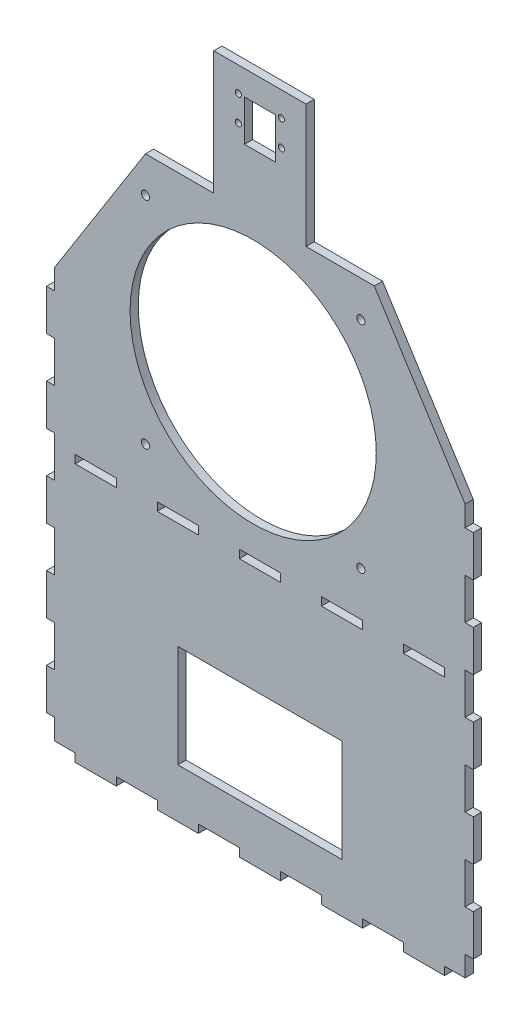
SolidWorks part; units mm, degrees
ref_plane "Přední rovina" through (0, 0, 0) normal (0, 0, 1) x (1, 0, 0)
ref_plane "Horní rovina" through (0, 0, 0) normal (0, 1, 0) x (1, 0, 0)
ref_plane "Pravá rovina" through (0, 0, 0) normal (1, 0, 0) x (0, 0, -1)
sketch "Skica1" plane through (0, 0, 0) normal (0, 0, 1) x (1, 0, 0)
  line L0 (-22.5981, -113.24) -> (-22.5981, -95.4761)
  line L1 (-122.5981, -113.24) -> (77.4019, -113.24)
  line L2 (-122.5981, -113.24) -> (-122.5981, 156.76)
  line L3 (-122.5981, 156.76) -> (77.4019, 156.76)
  line L4 (77.4019, -113.24) -> (77.4019, 156.76)
  line L5 (-112.5981, -113.24) -> (-92.5981, -113.24)
  line L6 (-112.5981, -113.24) -> (-112.5981, -117.24)
  line L7 (-112.5981, -117.24) -> (-92.5981, -117.24)
  line L8 (-92.5981, -113.24) -> (-92.5981, -117.24)
  line L9 (-72.5981, -113.24) -> (-52.5981, -113.24)
  line L10 (-72.5981, -113.24) -> (-72.5981, -117.24)
  line L11 (-72.5981, -117.24) -> (-52.5981, -117.24)
  line L12 (-52.5981, -113.24) -> (-52.5981, -117.24)
  line L13 (-32.5981, -113.24) -> (-12.5981, -113.24)
  line L14 (-32.5981, -113.24) -> (-32.5981, -117.24)
  line L15 (-32.5981, -117.24) -> (-12.5981, -117.24)
  line L16 (-12.5981, -113.24) -> (-12.5981, -117.24)
  line L17 (27.4019, -117.24) -> (7.4019, -117.24)
  line L18 (7.4019, -113.24) -> (7.4019, -117.24)
  line L19 (27.4019, -113.24) -> (7.4019, -113.24)
  line L20 (27.4019, -113.24) -> (27.4019, -117.24)
  line L21 (67.4019, -117.24) -> (47.4019, -117.24)
  line L22 (47.4019, -113.24) -> (47.4019, -117.24)
  line L23 (67.4019, -113.24) -> (47.4019, -113.24)
  line L24 (67.4019, -113.24) -> (67.4019, -117.24)
  line L25 (77.4019, 36.76) -> (81.4019, 36.76)
  line L26 (-122.5981, -103.24) -> (-126.5981, -103.24)
  line L27 (-122.5981, -103.24) -> (-122.5981, -83.24)
  line L28 (-122.5981, -83.24) -> (-126.5981, -83.24)
  line L29 (-126.5981, -103.24) -> (-126.5981, -83.24)
  line L30 (-122.5981, -63.24) -> (-126.5981, -63.24)
  line L31 (-122.5981, -63.24) -> (-122.5981, -43.24)
  line L32 (-122.5981, -43.24) -> (-126.5981, -43.24)
  line L33 (-126.5981, -63.24) -> (-126.5981, -43.24)
  line L34 (-122.5981, -23.24) -> (-126.5981, -23.24)
  line L35 (-122.5981, -23.24) -> (-122.5981, -3.24)
  line L36 (-122.5981, -3.24) -> (-126.5981, -3.24)
  line L37 (-126.5981, -23.24) -> (-126.5981, -3.24)
  line L38 (-122.5981, 16.76) -> (-126.5981, 16.76)
  line L39 (-122.5981, 16.76) -> (-122.5981, 36.76)
  line L40 (-122.5981, 36.76) -> (-126.5981, 36.76)
  line L41 (-126.5981, 16.76) -> (-126.5981, 36.76)
  line L42 (81.4019, 16.76) -> (81.4019, 36.76)
  line L43 (77.4019, 16.76) -> (81.4019, 16.76)
  line L44 (77.4019, 16.76) -> (77.4019, 36.76)
  line L45 (77.4019, -3.24) -> (81.4019, -3.24)
  line L46 (81.4019, -23.24) -> (81.4019, -3.24)
  line L47 (77.4019, -23.24) -> (81.4019, -23.24)
  line L48 (77.4019, -23.24) -> (77.4019, -3.24)
  line L49 (77.4019, -43.24) -> (81.4019, -43.24)
  line L50 (81.4019, -63.24) -> (81.4019, -43.24)
  line L51 (77.4019, -63.24) -> (81.4019, -63.24)
  line L52 (77.4019, -63.24) -> (77.4019, -43.24)
  line L53 (77.4019, -83.24) -> (81.4019, -83.24)
  line L54 (81.4019, -103.24) -> (81.4019, -83.24)
  line L55 (77.4019, -103.24) -> (81.4019, -103.24)
  line L56 (77.4019, -103.24) -> (77.4019, -83.24)
  line L57 (-78.3799, 156.76) -> (-122.5981, 86.76)
  line L58 (-112.5981, 12.76) -> (-92.5981, 12.76)
  line L59 (-112.5981, 12.76) -> (-112.5981, 8.76)
  line L60 (-112.5981, 8.76) -> (-92.5981, 8.76)
  line L61 (-92.5981, 12.76) -> (-92.5981, 8.76)
  line L62 (-72.5981, 12.76) -> (-52.5981, 12.76)
  line L63 (-72.5981, 12.76) -> (-72.5981, 8.76)
  line L64 (-72.5981, 8.76) -> (-52.5981, 8.76)
  line L65 (-52.5981, 12.76) -> (-52.5981, 8.76)
  line L66 (-32.5981, 12.76) -> (-12.5981, 12.76)
  line L67 (-32.5981, 12.76) -> (-32.5981, 8.76)
  line L68 (-32.5981, 8.76) -> (-12.5981, 8.76)
  line L69 (-12.5981, 12.76) -> (-12.5981, 8.76)
  line L70 (7.4019, 12.76) -> (27.4019, 12.76)
  line L71 (7.4019, 12.76) -> (7.4019, 8.76)
  line L72 (7.4019, 8.76) -> (27.4019, 8.76)
  line L73 (27.4019, 12.76) -> (27.4019, 8.76)
  line L74 (47.4019, 12.76) -> (67.4019, 12.76)
  line L75 (47.4019, 12.76) -> (47.4019, 8.76)
  line L76 (47.4019, 8.76) -> (67.4019, 8.76)
  line L77 (67.4019, 12.76) -> (67.4019, 8.76)
  line L78 (-122.5981, 56.76) -> (-126.5981, 56.76)
  line L79 (-122.5981, 56.76) -> (-122.5981, 76.76)
  line L80 (-122.5981, 76.76) -> (-126.5981, 76.76)
  line L81 (-126.5981, 56.76) -> (-126.5981, 76.76)
  line L82 (33.1836, 156.76) -> (77.4019, 86.76)
  line L83 (77.4019, 76.76) -> (81.4019, 76.76)
  line L84 (81.4019, 56.76) -> (81.4019, 76.76)
  line L85 (77.4019, 56.76) -> (81.4019, 56.76)
  line L86 (77.4019, 56.76) -> (77.4019, 76.76)
  line L88 (-45.0981, 156.76) -> (-0.0981, 156.76)
  line L89 (-45.0981, 156.76) -> (-45.0981, 216.8991)
  line L90 (-45.0981, 216.8991) -> (-0.0981, 216.8991)
  line L91 (-0.0981, 156.76) -> (-0.0981, 216.8991)
  line L92 (-30.0981, 204.8991) -> (-15.0981, 204.8991)
  line L93 (-30.0981, 204.8991) -> (-30.0981, 184.8991)
  line L94 (-30.0981, 184.8991) -> (-15.0981, 184.8991)
  line L95 (-15.0981, 204.8991) -> (-15.0981, 184.8991)
  line L96 (-62.5981, -93.24) -> (17.4019, -93.24)
  line L97 (-62.5981, -93.24) -> (-62.5981, -43.24)
  line L98 (-62.5981, -43.24) -> (17.4019, -43.24)
  line L99 (17.4019, -93.24) -> (17.4019, -43.24)
  circle A0 centre (-25.8799, 86.76) radius 60
  circle A1 centre (-78.3799, 139.26) radius 2
  circle A2 centre (26.6201, 139.26) radius 2
  circle A3 centre (26.6201, 34.26) radius 2
  circle A4 centre (-78.3799, 34.26) radius 2
  circle A5 centre (-33.0981, 204.8991) radius 1.5
  circle A6 centre (-12.0981, 204.8991) radius 1.5
  circle A7 centre (-12.0981, 192.3991) radius 1.5
  circle A8 centre (-33.0981, 192.3991) radius 1.5
  point P89 (-122.5981, 86.76)
  point P93 (-78.3799, 156.76)
  dimension "D3" = 120
  dimension "D4" = 70
  dimension "D6" = 4
  dimension "D7" = 4
  dimension "D8" = 4
  dimension "D9" = 4
  dimension "D35" = 3
  dimension "D36" = 3
  dimension "D37" = 3
  dimension "D38" = 3
  dimension "D1" = 270
  dimension "D2" = 200
  dimension "D5" = 105
  dimension "D10" = 105
  dimension "D11" = 52.5
  dimension "D12" = 52.5
  dimension "D13" = 20
  dimension "D14" = 20
  dimension "D15" = 20
  dimension "D16" = 20
  dimension "D17" = 10
  dimension "D18" = 20
  dimension "D19" = 4
  dimension "D20" = 10
  dimension "D21" = 20
  dimension "D22" = 20
  dimension "D23" = 20
  dimension "D24" = 20
  dimension "D25" = 20
  dimension "D26" = 20
  dimension "D27" = 20
  dimension "D28" = 4
  dimension "D29" = 4
  dimension "D30" = 20
  dimension "D31" = 20
  dimension "D32" = 10
  dimension "D33" = 4
  dimension "D34" = 45
  dimension "D39" = 12.5
  dimension "D40" = 21
  dimension "D41" = 12
  dimension "D42" = 12
  dimension "D43" = 12
  dimension "D44" = 15
  dimension "D45" = 3
  dimension "D46" = 20
  dimension "D47" = 22.5
  dimension "D48" = 50
  dimension "D49" = 80
  dimension "D50" = 20
  dimension "D51" = 40
  dimension "D52" = 10
extrude "Přidat vysunutím1" add sketch "Skica1" along normal blind 4 contours L8 L1 L6 L7 | L41 L38 L2 L40 | L37 L34 L2 L36 | L1 L4 L3 L2 A4 A3 A2 A1 A0 L58 L61 L60 L59 L62 L65 | L42 L25 L44 L43 | L46 L45 L48 L47 | L50 L49 L52 L51 | L54 L53 L56 L55 | L21 L22 L23 L24 | L17 L18 L19 L20 | L15 L16 L13 L14 | L11 L12 L9 L10 | L29 L28 L27 L26 | L33 L32 L31 L30 | L79 L78 L81 L80 | L83 L84 L85 L86 | L89 L88 L91 L90 | L93 L92 L95 L94 | A7 | A8 | A5 | A6 region at (-21.5374, 1.2835, 0) region at (-102.5981, -115.24, 0) region at (-124.5981, -13.24, 0) region at (-124.5981, 26.76, 0)
